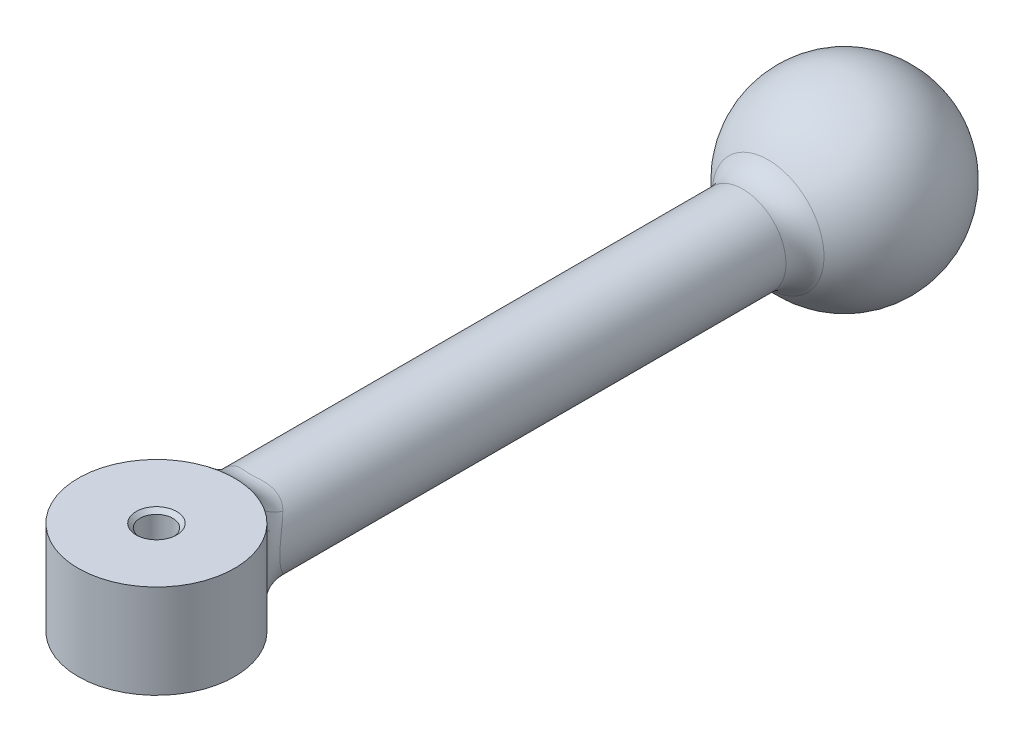
SolidWorks part; units mm, degrees
material "高韧性光敏树脂"
ref_plane "前视基准面" through (0, 0, 0) normal (0, 0, 1) x (1, 0, 0)
ref_plane "上视基准面" through (0, 0, 0) normal (0, 1, 0) x (1, 0, 0)
ref_plane "右视基准面" through (0, 0, 0) normal (1, 0, 0) x (0, 0, -1)
sketch "草图1" plane through (0, 0, 0) normal (0, 0, 1) x (1, 0, 0)
  line L0 (0, 2.42) -> (0, -2.42)
  circle A0 centre (0, 0) radius 2.42
  dimension "D1" = 4.84
revolve "旋转1" add sketch "草图1" angle 360 about L0 region at (-1.0271, 0, 0)
sketch "草图2" plane through (0, 0, 0) normal (0, 0, 1) x (1, 0, 0)
  circle A0 centre (0, 0) radius 1.1
  dimension "D1" = 2.2
extrude "凸台-拉伸1" add sketch "草图2" along normal blind 17.6064
sketch "草图3" plane through (0, 0, 0) normal (0, 1, 0) x (1, 0, 0)
  line L0 (-1.1, -17.6064) -> (1.1, -17.6064) construction
  circle A0 centre (0, -17.6064) radius 2
  circle A1 centre (0, -17.6064) radius 0.42
  dimension "D1" = 0.84
  dimension "D2" = 4
extrude "切除-拉伸1" cut sketch "草图3" against normal through all both and the other way through all contours A0
extrude "凸台-拉伸2" add sketch "草图3<3>" along normal mid plane 2.4
sketch "草图3<3>" plane through (0, 0, 0) normal (0, 1, 0) x (1, 0, 0) same geometry as "草图3"
ref_axis "基准轴1" through (0, 0, 16.0148) along (0, 0, -1)
chamfer "倒角1" distance 0.1 angle 45 2 edges at (0, 1.2, 18.0264) (0, -1.2, 18.0264)
ref_plane "基准面1" through (0, 0, 5) normal (0, 0, 1) x (1, 0, 0)
fillet "圆角1" radius 0.8 1 edges at (-1.1, 0, 2.1556)
fillet "圆角2" radius 0.8 1 edges at (1.096, 0.0936, 15.9334)
equation "\"d\"= 10"
equation "\"l\"= 13.52"
equation "\"L1\"= 8.283"
equation "\"th\"= 52.956771"
equation "\"k\"= 0.8"
equation "\"D1@凸台-拉伸1\"=\"l\"*\"k\""
